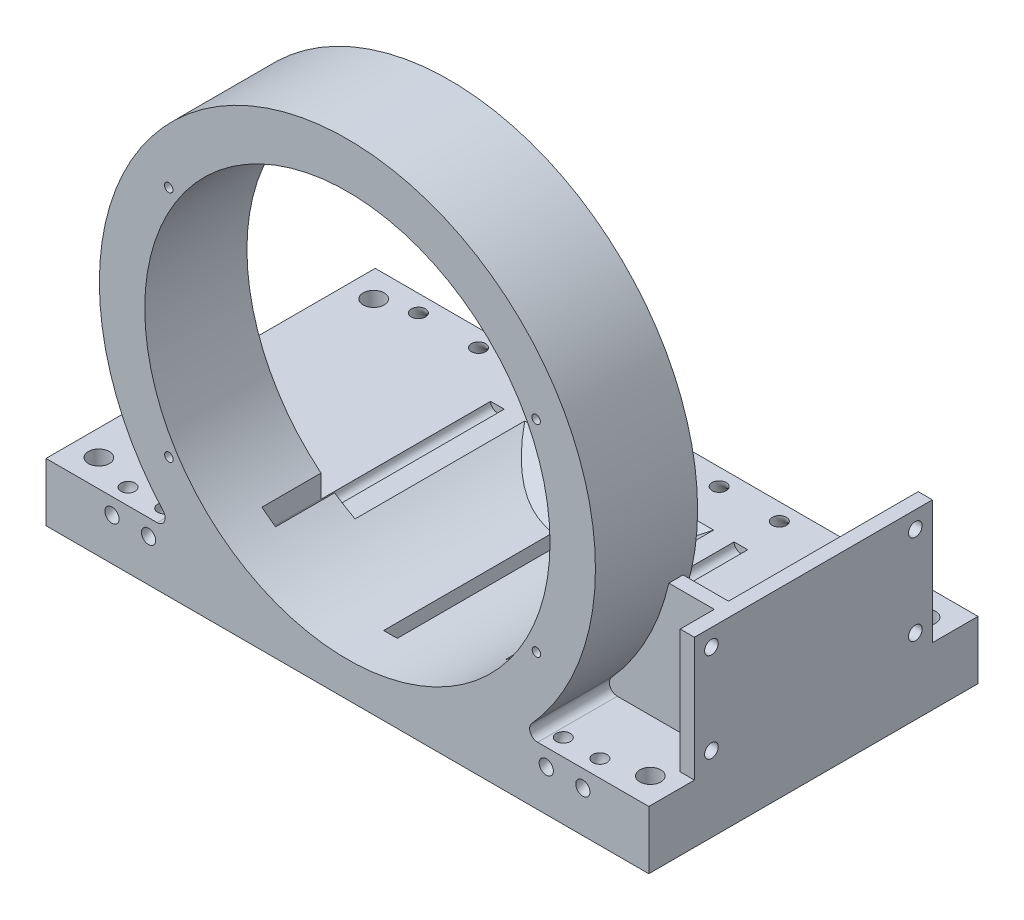
SolidWorks part; units mm, degrees
ref_plane "Front Plane" through (0, 0, 0) normal (0, 0, 1) x (1, 0, 0)
ref_plane "Top Plane" through (0, 0, 0) normal (0, 1, 0) x (1, 0, 0)
ref_plane "Right Plane" through (0, 0, 0) normal (1, 0, 0) x (0, 0, -1)
sketch "Sketch1" plane through (0, 0, 0) normal (0, 0, 1) x (1, 0, 0)
  line L0 (-34.1117, 43.7782) -> (34.1117, 43.7782)
  line L4 (28.448, -40.0843) -> (28.448, -35.2709)
  line L5 (-67.4363, -40.1112) -> (-38.3566, -40.1112)
  line L6 (-67.4363, -40.1112) -> (-67.4363, -53.1541)
  line L7 (-67.4363, -53.1541) -> (67.4363, -53.1541)
  line L8 (67.4363, -40.1112) -> (67.4363, -53.1541)
  line L9 (1.2065, -45.2975) -> (1.2065, -49.1871)
  line L10 (-1.2065, -45.2975) -> (-1.2065, -49.1871)
  line L11 (-45.339, 0) -> (45.339, 0) construction
  line L12 (-28.448, -35.2709) -> (-28.448, -40.0843)
  line L13 (38.3566, -40.1112) -> (67.4363, -40.1112)
  line L14 (26.035, -37.0877) -> (26.035, -40.0843)
  line L15 (0, 45.339) -> (0, -45.339) construction
  line L16 (-26.035, -40.0843) -> (-26.035, -37.0877)
  line L17 (-39.989, 26.0985) -> (-39.9308, -26.0985) construction
  line L18 (42.2197, 22.3102) -> (42.298, -22.7748) construction
  arc A1 (-26.035, -37.1188) -> (-1.2065, -45.3229) centre (0, 0) ccw
  arc A2 (-34.1117, 43.7782) -> (-38.3566, -40.1112) centre (0, 0) ccw
  circle A3 centre (-39.989, 26.0985) radius 0.9525
  arc A4 (38.3566, -40.1112) -> (34.1117, 43.7782) centre (0, 0) ccw
  circle A5 centre (-39.9308, -26.0985) radius 0.9525
  circle A6 centre (42.298, -22.7748) radius 0.9525
  circle A7 centre (42.2197, 22.3102) radius 0.9525
  arc A9 (-1.2065, -49.1871) -> (1.2065, -49.1871) centre (0, -49.1871) ccw
  arc A10 (-28.448, -40.0843) -> (-26.035, -40.0843) centre (-27.2415, -40.0843) ccw
  arc A11 (1.2065, -45.3229) -> (26.035, -37.1188) centre (0, 0) ccw
  arc A12 (26.035, -40.0843) -> (28.448, -40.0843) centre (27.2415, -40.0843) ccw
  arc A13 (28.448, -35.3035) -> (-28.448, -35.3035) centre (0, 0) ccw
  point P8 (0, -45.339)
  point P24 (-39.9599, 0)
  point P25 (42.2589, -0.2323)
  point P26 (0, 0)
  point P28 (0, 0)
  dimension "D1" = 90.678
  dimension "D2" = 10.16
  dimension "D4" = 1.905
  dimension "D5" = 1.905
  dimension "D6" = 1.905
  dimension "D7" = 1.905
  dimension "D10" = 82.296
  dimension "D3" = 2.413
  dimension "D8" = 52.197
  dimension "D9" = 45.085
  dimension "D11" = 82.296
  dimension "D12" = 47.752
  dimension "D13" = 47.752
extrude "Boss-Extrude1" add sketch "Sketch1" along normal blind 22.86 contours L13 A4 L0 A1 A2 L5 L6 L7 L8 region at (-22.9528, 42.1173, 0)
sketch "Sketch2" plane through (0, 0, 0) normal (0, 0, -1) x (-1, 0, 0)
  line L0 (21.1356, -40.1112) -> (26.0353, -40.1112)
  line L1 (-67.4363, -53.1541) -> (67.4363, -53.1541)
  line L2 (-67.4363, -53.1541) -> (-67.4363, -40.1112)
  line L3 (-67.4363, -40.1112) -> (-28.4477, -40.1112)
  line L4 (67.4363, -53.1541) -> (67.4363, -40.1112)
  line L5 (1.2065, -49.1871) -> (1.2065, -45.3229)
  line L6 (28.4477, -40.1112) -> (67.4363, -40.1112)
  line L7 (-1.2065, -45.3229) -> (-1.2065, -49.1871)
  line L8 (-26.0353, -40.1112) -> (-21.1356, -40.1112)
  arc A0 (-21.1356, -40.1112) -> (-1.2065, -45.3229) centre (0, 0) ccw
  arc A1 (-28.4477, -40.1112) -> (-26.0353, -40.1112) centre (-27.2415, -40.0843) ccw
  arc A2 (-1.2065, -49.1871) -> (1.2065, -49.1871) centre (0, -49.1871) ccw
  arc A3 (26.0353, -40.1112) -> (28.4477, -40.1112) centre (27.2415, -40.0843) ccw
  arc A4 (1.2065, -45.3229) -> (21.1356, -40.1112) centre (0, 0) ccw
extrude "Boss-Extrude2" add sketch "Sketch2" along normal blind 50.8 contours L2 L3 A1 L8 A0 L7 A2 L5 A4 L0 A3 L6 L4 L1
sketch "Sketch3" plane through (0, 0, 0) normal (0, 0, -1) x (-1, 0, 0)
  line L0 (-28.448, 40.2554) -> (-28.448, 35.2709)
  line L1 (-28.448, 35.2709) -> (-26.035, 37.0877)
  line L2 (-26.035, 37.0877) -> (-26.035, 40.2554)
  line L3 (28.448, 40.2554) -> (28.448, 35.3035)
  line L4 (28.448, 35.3035) -> (26.0792, 37.0877)
  line L5 (26.0792, 37.0877) -> (26.035, 40.2554)
  line L6 (-25.7175, 36.9294) -> (-25.7175, 40.2554)
  line L7 (-28.7655, 40.2554) -> (-28.7655, 34.6344)
  line L8 (-28.7655, 34.6344) -> (-25.7175, 36.9294)
  line L9 (25.7639, 36.9278) -> (25.7175, 40.251)
  line L10 (28.7655, 34.6668) -> (25.7639, 36.9278)
  line L11 (28.7655, 40.2554) -> (28.7655, 34.6668)
  arc A0 (-26.035, 40.2554) -> (-28.448, 40.2554) centre (-27.2415, 40.2554) ccw
  arc A1 (28.448, 40.2554) -> (26.0355, 40.2217) centre (27.2415, 40.2554) ccw
  arc A2 (28.448, -35.3035) -> (11.7939, 43.7782) centre (0, 0) ccw construction
  arc A3 (-25.7175, 40.2554) -> (-28.7655, 40.2554) centre (-27.2415, 40.2554) ccw
  arc A4 (28.7655, 40.2554) -> (25.7181, 40.2129) centre (27.2415, 40.2554) ccw
  arc M5 (11.7939, 43.7782) -> (28.448, -35.3035) centre (0, 0) cw
  dimension "D1" = 0.3175
extrude "Cut-Extrude1" cut sketch "Sketch3" against normal blind 13.208 contours L3 A1 L5 M5 | L2 A0 L0 L1 region at (27.3142, 38.671, 0) region at (-27.3223, 38.7004, 0)
sketch "Sketch4" plane through (0, 0, 22.86) normal (0, 0, 1) x (1, 0, 0)
  line L0 (-26.035, -40.0843) -> (-26.035, -37.1188)
  line L2 (-28.448, -35.3035) -> (-28.448, -40.0843)
  line L3 (-1.2065, -45.3229) -> (-1.2065, -49.1871)
  line L5 (1.2065, -45.2975) -> (1.2065, -49.1871)
  line L6 (28.448, -40.0843) -> (28.448, -35.3035)
  line L7 (1.1905, -45.3234) -> (1.2065, -45.2975)
  line L8 (26.035, -37.1188) -> (26.035, -40.0843)
  arc A0 (-28.448, -40.0843) -> (-26.035, -40.0843) centre (-27.2415, -40.0843) ccw
  arc A1 (-1.2065, -49.1871) -> (1.2065, -49.1871) centre (0, -49.1871) ccw
  arc A2 (26.035, -40.0843) -> (28.448, -40.0843) centre (27.2415, -40.0843) ccw
  arc A3 (-28.448, -35.3035) -> (-26.035, -37.1188) centre (0, 0) ccw
  arc A4 (-1.2065, -45.3229) -> (1.2065, -45.3229) centre (0, 0) ccw
  arc A5 (26.035, -37.1188) -> (28.448, -35.3035) centre (0, 0) ccw
  line M14 (28.448, -35.3035) -> (28.448, -40.0843)
  arc M15 (28.448, -40.0843) -> (26.035, -40.0843) centre (27.2415, -40.0843) cw
  line M16 (26.035, -40.0843) -> (26.035, -37.1188)
  line M18 (1.2065, -45.3229) -> (1.2065, -49.1871)
  arc M19 (1.2065, -49.1871) -> (-1.2065, -49.1871) centre (0, -49.1871) cw
  line M20 (-1.2065, -49.1871) -> (-1.2065, -45.3229)
  line M22 (-26.035, -37.1188) -> (-26.035, -40.0843)
  arc M23 (-26.035, -40.0843) -> (-28.448, -40.0843) centre (-27.2415, -40.0843) cw
  line M24 (-28.448, -40.0843) -> (-28.448, -35.3035)
extrude "Boss-Extrude3" add sketch "Sketch4" against normal blind 9.652 contours A3 M24 M23 M22 | A4 M20 M19 M18 | A5 M16 M15 M14 region at (-27.3175, -38.611, 22.86) region at (0, -47.7417, 22.86) region at (27.3175, -38.611, 22.86)
sketch "Sketch6" plane through (67.4363, 0, 0) normal (1, 0, 0) x (0, 0, -1)
  line L2 (20.8189, -46.8236) -> (20.8189, -53.1541)
  line L3 (50.8, -40.1112) -> (50.8, -45.3976)
  line L5 (-22.86, -53.1541) -> (50.8, -53.1541) construction
  line L6 (20.8189, -53.1541) -> (50.8, -53.1541)
  line L9 (50.8, -53.1541) -> (50.8, -45.3976)
  line L10 (50.8, -53.1541) -> (50.8, -40.1112) construction
  line L12 (50.8, -40.1112) -> (37.9477, -40.1112)
  line L13 (-22.86, -40.1112) -> (50.8, -40.1112) construction
  line L14 (37.9477, -40.1112) -> (20.8189, -46.8236)
extrude "Boss-Extrude5" add sketch "Sketch6" against normal blind 116.84 contours L14 L2 L6 L9 L3 L12
sketch "Sketch7" plane through (0, -53.1541, 0) normal (0, -1, 0) x (1, 0, 0)
  line L0 (-61.6911, -44.7061) -> (-61.6911, 16.7661) construction
  line L1 (0, -13.97) -> (-61.6911, 16.7661)
  line L2 (-61.6911, 16.7661) -> (61.6911, -44.7061)
  line L3 (0, -13.97) -> (-61.6911, -13.97) construction
  line L4 (0, 22.86) -> (0, -50.8) construction
  line L5 (-67.4363, 22.86) -> (67.4363, 22.86) construction
  line L6 (67.4363, -50.8) -> (-67.4363, -50.8) construction
  circle A0 centre (-61.6911, 16.7661) radius 2.3495
  circle A1 centre (61.6911, -44.7061) radius 2.3495
  circle A2 centre (-61.6911, -44.7061) radius 2.3495
  circle A3 centre (61.6911, 16.7661) radius 2.3495
  dimension "D3" = 4.699
  dimension "D4" = 4.699
  dimension "D1" = 68.9238
  dimension "D2" = 137.8477
  dimension "D5" = 61.4723
extrude "Cut-Extrude2" cut sketch "Sketch7" against normal blind 25.4 contours A0 | A2 | A1 | A3 region at (-63.9134, -53.1541, 17.2891) region at (-61.6911, -53.1541, -44.7061)
sketch "Sketch8" plane through (0, -40.1112, 0) normal (0, 1, 0) x (1, 0, 0)
  line L0 (-67.4363, 50.8) -> (67.4363, 50.8)
  line L1 (-67.4363, 50.8) -> (-67.4363, 46.99)
  line L2 (-67.4363, -22.86) -> (-67.4363, 50.8) construction
  line L3 (-67.4363, 46.99) -> (67.4363, 46.99) construction
  line L4 (67.4363, -22.86) -> (67.4363, 50.8) construction
  line L5 (-67.4363, -22.86) -> (-67.4363, -17.78)
  line L6 (-67.4363, -17.78) -> (67.4363, -17.78) construction
  line L7 (-0.1263, 46.99) -> (0, -17.78) construction
  circle A0 centre (-53.9743, 46.99) radius 1.5875
  circle A1 centre (-40.5123, 46.99) radius 1.5875
  circle A2 centre (-27.0503, 46.99) radius 1.5875
  circle A3 centre (-13.5883, 46.99) radius 1.5875
  circle A4 centre (-0.1263, 46.99) radius 1.5875
  circle A5 centre (13.3357, 46.99) radius 1.5875
  circle A6 centre (26.7977, 46.99) radius 1.5875
  circle A7 centre (40.2597, 46.99) radius 1.5875
  circle A8 centre (53.7217, 46.99) radius 1.5875
  circle A9 centre (53.7217, -17.78) radius 1.5875
  circle A10 centre (44.6271, -17.78) radius 1.5875
  circle A11 centre (-53.7213, -17.9895) radius 1.5875
  circle A12 centre (-44.6267, -17.9541) radius 1.5875
  dimension "D1" = 3.175
  dimension "D6" = 3.175
  dimension "D7" = 3.175
  dimension "D2" = 3.81
  dimension "D3" = 13.462
  dimension "D5" = 5.08
  dimension "D4" = 9
revolve "Cut-Revolve1" cut sketch "Sketch8" angle 360 about L0 region at (-53.9743, -40.1112, -46.99) region at (-40.5123, -40.1112, -46.99) region at (-27.0503, -40.1112, -46.99) region at (-13.5883, -40.1112, -46.99) region at (-0.1263, -40.1112, -46.99) region at (13.3357, -40.1112, -46.99) region at (26.7977, -40.1112, -46.99) region at (40.2597, -40.1112, -46.99) region at (53.7217, -40.1112, -46.99)
sketch "Sketch9" plane through (0, -40.1112, 0) normal (0, 1, 0) x (1, 0, 0)
  line L0 (-67.4363, -22.86) -> (-67.4363, -19.05)
  line L1 (-67.4363, -22.86) -> (-67.4363, 50.8) construction
  line L2 (-67.4363, -19.05) -> (67.4363, -19.05) construction
  line L3 (67.4363, -22.86) -> (67.4363, 50.8) construction
  line L4 (0, -19.05) -> (-0.1263, 45.4025)
  circle A0 centre (44.4978, -19.05) radius 1.5875
  circle A1 centre (52.6808, -19.05) radius 1.5875
  circle A2 centre (-0.1263, 46.99) radius 1.5875 construction
  circle A3 centre (-52.6804, -19.2565) radius 1.5875
  circle A4 centre (-44.4975, -19.2244) radius 1.5875
  dimension "D2" = 3.175
  dimension "D3" = 3.175
  dimension "D1" = 3.81
revolve "Cut-Revolve2" cut sketch "Sketch9" angle 360 about axis through (0, -40.1112, 22.86) along (1, 0, 0) region at (-52.6804, -40.1112, 18.4698) region at (52.6808, -40.1112, 18.3762) region at (52.6808, -40.1112, 19.7238) region at (44.4978, -40.1112, 18.3762) region at (44.4978, -40.1112, 19.7238) region at (-44.4975, -40.1112, 18.4555) region at (-44.4975, -40.1112, 19.805) region at (-52.6804, -40.1112, 19.8201)
fillet "Fillet1" radius 1.778 2 edges at (-38.3566, -40.1112, 11.43) (38.3566, -40.1112, 11.43)
sketch "Sketch11" plane through (0, 0, 0) normal (0, 0, -1) x (-1, 0, 0)
  line L1 (28.448, -35.3035) -> (28.448, -40.0843) construction
  line L2 (28.4477, -40.1112) -> (42.5584, -40.1112) construction
  line L3 (34.1117, 43.7782) -> (11.7939, 43.7782) construction
  line L5 (-26.035, 40.2554) -> (-26.035, 37.1188) construction
  line L6 (-11.7939, 43.7782) -> (-34.1117, 43.7782) construction
  line L7 (-42.5584, -40.1112) -> (-28.4477, -40.1112) construction
  line L8 (-28.448, -40.0843) -> (-28.448, -35.3035) construction
  line L9 (-28.448, 35.3035) -> (-28.448, 40.2554) construction
  line L11 (28.448, -35.3035) -> (28.448, -40.0843)
  line L12 (28.4477, -40.1112) -> (42.5584, -40.1112)
  line L13 (34.1117, 43.7782) -> (11.7939, 43.7782)
  line L15 (-26.035, 40.2554) -> (-26.035, 37.1188)
  line L16 (-11.7939, 43.7782) -> (-34.1117, 43.7782)
  line L17 (-42.5584, -40.1112) -> (-28.4477, -40.1112)
  line L18 (-28.448, -40.0843) -> (-28.448, -35.3035)
  line L19 (-28.448, 35.3035) -> (-28.448, 40.2554)
  line L20 (-28.829, 40.2554) -> (-28.829, 34.9931)
  line L21 (-25.654, 40.2554) -> (-25.654, 37.3831)
  line L22 (-11.7939, 43.7782) -> (11.7939, 43.7782)
  line L23 (0, 43.7782) -> (0, 33.6339)
  line L24 (-25.7175, -40.0843) -> (-25.7175, -36.9533)
  line L25 (-28.7655, -34.6335) -> (-28.7655, -40.0843)
  line L26 (-26.0353, -40.1112) -> (-21.1356, -40.1112)
  line L27 (-26.035, -37.1188) -> (-26.035, -40.0843)
  line L28 (-26.0353, -40.1112) -> (-21.1356, -40.1112)
  line L29 (-26.035, -37.1188) -> (-26.035, -40.0843)
  line L30 (-28.448, -35.3035) -> (-28.448, -40.0843)
  line L31 (-26.035, -40.0843) -> (-26.035, -37.1188)
  line L32 (-28.448, -35.3035) -> (-28.448, -40.0843)
  line L33 (-26.035, -40.0843) -> (-26.035, -37.1188)
  line L34 (-1.2065, -45.3229) -> (-1.2065, -49.1871)
  line L35 (1.2065, -49.1871) -> (1.2065, -45.3229)
  line L36 (-1.2065, -45.3229) -> (-1.2065, -49.1871)
  line L37 (1.2065, -49.1871) -> (1.2065, -45.3229)
  line L38 (1.524, -49.1871) -> (1.524, -44.9957)
  line L39 (-1.524, -44.9957) -> (-1.524, -49.1871)
  line L40 (1.524, -44.9957) -> (1.524, -49.1871)
  line L41 (-1.524, -49.1871) -> (-1.524, -44.9957)
  line L42 (-1.2065, -49.1871) -> (-1.2065, -45.3229)
  line L43 (1.2065, -45.3229) -> (1.2065, -49.1871)
  line L44 (26.035, -40.0843) -> (26.035, -37.1188)
  line L45 (28.448, -35.3035) -> (28.448, -40.0843)
  line L46 (26.035, -37.1188) -> (26.035, -40.0843)
  line L47 (26.0353, -40.1112) -> (21.1356, -40.1112)
  line L48 (28.7655, -34.6335) -> (28.7655, -40.0843)
  line L49 (25.7175, -40.0843) -> (25.7175, -36.9533)
  line L50 (25.654, 40.2554) -> (25.654, 37.3831)
  line L51 (28.829, 40.2554) -> (28.829, 34.9931)
  line L53 (28.448, -40.0843) -> (28.448, -35.3035)
  line L54 (42.5584, -40.1112) -> (28.4477, -40.1112)
  line L55 (11.7939, 43.7782) -> (34.1117, 43.7782)
  line L62 (28.448, 40.2554) -> (28.448, 35.3035)
  line L63 (28.448, -35.3035) -> (28.448, -40.0843)
  line L64 (28.4477, -40.1112) -> (42.5584, -40.1112)
  line L65 (34.1117, 43.7782) -> (11.7939, 43.7782)
  line L66 (26.0792, 37.0877) -> (26.035, 40.2554)
  line L68 (28.448, -35.3035) -> (28.448, -40.0843)
  line L69 (28.4477, -40.1112) -> (42.5584, -40.1112)
  line L70 (34.1117, 43.7782) -> (11.7939, 43.7782)
  arc A0 (28.448, -35.3035) -> (28.448, 35.3035) centre (0, 0) ccw construction
  arc A1 (28.4477, -40.1112) -> (28.448, -40.0843) centre (27.2415, -40.0843) ccw construction
  arc A2 (41.2373, -37.1433) -> (42.5584, -40.1112) centre (42.5584, -38.3332) ccw construction
  arc A3 (41.2373, -37.1433) -> (34.1117, 43.7782) centre (0, 0) ccw construction
  arc A4 (26.0792, 37.0877) -> (11.7939, 43.7782) centre (0, 0) ccw construction
  arc A5 (28.448, 40.2554) -> (26.035, 40.2554) centre (27.2415, 40.2554) ccw construction
  arc A6 (-26.035, 40.2554) -> (-28.448, 40.2554) centre (-27.2415, 40.2554) ccw construction
  arc A7 (-11.7939, 43.7782) -> (-26.035, 37.1188) centre (0, 0) ccw construction
  arc A8 (-34.1117, 43.7782) -> (-41.2373, -37.1433) centre (0, 0) ccw construction
  arc A9 (-42.5584, -40.1112) -> (-41.2373, -37.1433) centre (-42.5584, -38.3332) ccw construction
  arc A10 (-28.448, -40.0843) -> (-28.4477, -40.1112) centre (-27.2415, -40.0843) ccw construction
  arc A11 (-28.448, 35.3035) -> (-28.448, -35.3035) centre (0, 0) ccw construction
  arc A12 (28.448, -35.3035) -> (28.448, 35.3035) centre (0, 0) ccw
  arc A13 (28.4477, -40.1112) -> (28.448, -40.0843) centre (27.2415, -40.0843) ccw
  arc A14 (41.2373, -37.1433) -> (42.5584, -40.1112) centre (42.5584, -38.3332) ccw
  arc A15 (41.2373, -37.1433) -> (34.1117, 43.7782) centre (0, 0) ccw
  arc A16 (26.0792, 37.0877) -> (11.7939, 43.7782) centre (0, 0) ccw
  arc A18 (-26.035, 40.2554) -> (-28.448, 40.2554) centre (-27.2415, 40.2554) ccw
  arc A19 (-11.7939, 43.7782) -> (-26.035, 37.1188) centre (0, 0) ccw
  arc A20 (-34.1117, 43.7782) -> (-41.2373, -37.1433) centre (0, 0) ccw
  arc A21 (-42.5584, -40.1112) -> (-41.2373, -37.1433) centre (-42.5584, -38.3332) ccw
  arc A22 (-28.448, -40.0843) -> (-28.4477, -40.1112) centre (-27.2415, -40.0843) ccw
  arc A23 (-28.448, 35.3035) -> (-28.448, -35.3035) centre (0, 0) ccw
  circle A24 centre (-27.2415, 40.2554) radius 1.5875
  arc A25 (-28.7655, -40.0843) -> (-25.7175, -40.0843) centre (-27.2415, -40.0843) ccw
  arc A26 (-28.7655, -34.6335) -> (-25.7175, -36.9533) centre (0, 0) ccw
  arc A27 (-26.0353, -40.1112) -> (-26.035, -40.0843) centre (-27.2415, -40.0843) ccw
  arc A28 (-26.035, -37.1188) -> (-21.1356, -40.1112) centre (0, 0) ccw
  arc A29 (-26.0353, -40.1112) -> (-26.035, -40.0843) centre (-27.2415, -40.0843) ccw
  arc A30 (-26.035, -37.1188) -> (-21.1356, -40.1112) centre (0, 0) ccw
  arc A31 (-28.448, -35.3035) -> (-26.035, -37.1188) centre (0, 0) ccw
  arc A32 (-28.448, -40.0843) -> (-26.035, -40.0843) centre (-27.2415, -40.0843) ccw
  arc A33 (-28.448, -35.3035) -> (-26.035, -37.1188) centre (0, 0) ccw
  arc A34 (-28.448, -40.0843) -> (-26.035, -40.0843) centre (-27.2415, -40.0843) ccw
  arc A35 (-1.2065, -45.3229) -> (1.2065, -45.3229) centre (0, 0) ccw
  arc A36 (-1.2065, -49.1871) -> (1.2065, -49.1871) centre (0, -49.1871) ccw
  arc A37 (-1.2065, -45.3229) -> (1.2065, -45.3229) centre (0, 0) ccw
  arc A38 (-1.2065, -49.1871) -> (1.2065, -49.1871) centre (0, -49.1871) ccw
  arc A39 (-1.524, -49.1871) -> (1.524, -49.1871) centre (0, -49.1871) ccw
  arc A40 (-1.524, -44.9957) -> (1.524, -44.9957) centre (0, 0) ccw
  arc A41 (28.448, -40.0843) -> (26.035, -40.0843) centre (27.2415, -40.0843) cw
  arc A42 (28.448, -35.3035) -> (26.035, -37.1188) centre (0, 0) cw
  arc A43 (26.035, -37.1188) -> (21.1356, -40.1112) centre (0, 0) cw
  arc A44 (26.0353, -40.1112) -> (26.035, -40.0843) centre (27.2415, -40.0843) cw
  arc A45 (28.7655, -34.6335) -> (25.7175, -36.9533) centre (0, 0) cw
  arc A46 (28.7655, -40.0843) -> (25.7175, -40.0843) centre (27.2415, -40.0843) cw
  arc A48 (28.448, 35.3035) -> (28.448, -35.3035) centre (0, 0) cw
  arc A49 (28.448, -40.0843) -> (28.4477, -40.1112) centre (27.2415, -40.0843) cw
  arc A50 (42.5584, -40.1112) -> (41.2373, -37.1433) centre (42.5584, -38.3332) cw
  arc A51 (34.1117, 43.7782) -> (41.2373, -37.1433) centre (0, 0) cw
  arc A52 (11.7939, 43.7782) -> (26.035, 37.1188) centre (0, 0) cw
  arc A54 (28.829, 40.2554) -> (25.654, 40.2554) centre (27.2415, 40.2554) ccw
  circle A55 centre (0, 0) radius 45.339
  arc A60 (28.448, -35.3035) -> (28.448, 35.3035) centre (0, 0) ccw
  arc A61 (28.4477, -40.1112) -> (28.448, -40.0843) centre (27.2415, -40.0843) ccw
  arc A62 (41.2373, -37.1433) -> (42.5584, -40.1112) centre (42.5584, -38.3332) ccw
  arc A63 (41.2373, -37.1433) -> (34.1117, 43.7782) centre (0, 0) ccw
  arc A64 (26.0792, 37.0877) -> (11.7939, 43.7782) centre (0, 0) ccw
  arc A65 (28.448, 40.2554) -> (26.035, 40.2554) centre (27.2415, 40.2554) ccw
  arc A66 (28.448, -35.3035) -> (28.448, 35.3035) centre (0, 0) ccw
  arc A67 (28.4477, -40.1112) -> (28.448, -40.0843) centre (27.2415, -40.0843) ccw
  arc A68 (41.2373, -37.1433) -> (42.5584, -40.1112) centre (42.5584, -38.3332) ccw
  arc A69 (41.2373, -37.1433) -> (34.1117, 43.7782) centre (0, 0) ccw
  arc A70 (26.0792, 37.0877) -> (11.7939, 43.7782) centre (0, 0) ccw
  arc M27 (-28.448, 40.2554) -> (-26.035, 40.2554) centre (-27.2415, 40.2554) cw
  line M28 (-26.035, 40.2554) -> (-26.035, 37.1188)
  arc M29 (-26.035, 37.1188) -> (-11.7939, 43.7782) centre (0, 0) cw
  arc M34 (-28.4477, -40.1112) -> (-28.448, -40.0843) centre (-27.2415, -40.0843) cw
  line M35 (-28.448, -40.0843) -> (-28.448, -35.3035)
  arc M36 (-28.448, -35.3035) -> (-28.448, 35.3035) centre (0, 0) cw
  line M37 (-28.448, 35.3035) -> (-28.448, 40.2554)
  dimension "D1" = 3.175
  dimension "D2" = 0
  dimension "D3" = 0
  dimension "D4" = 0
  dimension "D5" = 0.3175
  dimension "D6" = 0.3175
  dimension "D7" = 0
extrude "Cut-Extrude3" cut sketch "Sketch11" against normal up to surface (13.208 mm away) contours A24 L20 M36 M37 | A24 L19 M27 M28 | A24 L15 L21 M29 | A34 L17 A25 L28 | A30 L29 A29 L28 A25 L24 | L25 A25 L17 M34 M35 M36 | A40 L39 A39 L38 A38 L36 A37 L37 | A46 L48 A12 L11 A13 L12 | A46 L12 A41 L47 | A46 L47 A41 L44 A43 L49 | A16 region at (-28.6081, -37.6424, 0) region at (-25.8783, -38.6696, 0) region at (-28.6065, -40.1452, 0) region at (-28.6866, 35.2073, 0) region at (-1.462, -47.2502, 0) region at (25.837, 38.4116, 0) region at (27.2415, -41.5744, 0) region at (25.8783, -38.6696, 0) region at (25.7909, 39.7197, 0) region at (28.6081, -37.6424, 0) region at (28.6466, 37.3546, 0) up to face at (-27.2453, -38.4544, 13.208)
sketch "Sketch12" plane through (0, 0, 0) normal (0, 0, 1) x (1, 0, 0)
  line L0 (28.7653, -40.1112) -> (28.4477, -40.1112) construction
  line L1 (26.0353, -40.1112) -> (25.7177, -40.1112) construction
  line L2 (1.2065, -45.3229) -> (1.2065, -49.1871) construction
  line L3 (-1.2065, -49.1871) -> (-1.2065, -45.3229) construction
  line L4 (-1.524, -45.3134) -> (-1.524, -49.1871) construction
  line L5 (1.524, -49.1871) -> (1.524, -45.3134) construction
  line L6 (-25.7177, -40.1112) -> (-26.0353, -40.1112) construction
  line L7 (-28.4477, -40.1112) -> (-28.7653, -40.1112) construction
  line L8 (28.7653, -40.1112) -> (28.4477, -40.1112)
  line L9 (26.0353, -40.1112) -> (25.7177, -40.1112)
  line L10 (1.2065, -45.3229) -> (1.2065, -49.1871)
  line L11 (-1.2065, -49.1871) -> (-1.2065, -45.3229)
  line L12 (-1.524, -45.3134) -> (-1.524, -49.1871)
  line L13 (1.524, -49.1871) -> (1.524, -45.3134)
  line L14 (-25.7177, -40.1112) -> (-26.0353, -40.1112)
  line L15 (-28.4477, -40.1112) -> (-28.7653, -40.1112)
  line L16 (-28.4477, -40.1112) -> (-26.0353, -40.1112)
  line L17 (-1.2065, -45.3229) -> (1.2065, -45.3229)
  line L18 (26.0353, -40.1112) -> (28.4477, -40.1112)
  line L20 (1.524, -45.3134) -> (-1.524, -45.3134)
  line L21 (1.524, -45.3134) -> (1.524, -39.544)
  line L22 (1.524, -39.544) -> (-1.524, -39.544)
  line L23 (-1.524, -45.3134) -> (-1.524, -39.544)
  arc A0 (26.0353, -40.1112) -> (28.4477, -40.1112) centre (27.2415, -40.0843) ccw construction
  arc A1 (25.7177, -40.1112) -> (28.7653, -40.1112) centre (27.2415, -40.0843) ccw construction
  arc A2 (1.2065, -45.3229) -> (1.524, -45.3134) centre (0, 0) ccw construction
  arc A3 (-1.2065, -49.1871) -> (1.2065, -49.1871) centre (0, -49.1871) ccw construction
  arc A4 (-1.524, -45.3134) -> (-1.2065, -45.3229) centre (0, 0) ccw construction
  arc A5 (-1.524, -49.1871) -> (1.524, -49.1871) centre (0, -49.1871) ccw construction
  arc A6 (-28.4477, -40.1112) -> (-26.0353, -40.1112) centre (-27.2415, -40.0843) ccw construction
  arc A7 (-28.7653, -40.1112) -> (-25.7177, -40.1112) centre (-27.2415, -40.0843) ccw construction
  arc A8 (26.0353, -40.1112) -> (28.4477, -40.1112) centre (27.2415, -40.0843) ccw
  arc A9 (25.7177, -40.1112) -> (28.7653, -40.1112) centre (27.2415, -40.0843) ccw
  arc A10 (1.2065, -45.3229) -> (1.524, -45.3134) centre (0, 0) ccw
  arc A11 (-1.2065, -49.1871) -> (1.2065, -49.1871) centre (0, -49.1871) ccw
  arc A12 (-1.524, -45.3134) -> (-1.2065, -45.3229) centre (0, 0) ccw
  arc A13 (-1.524, -49.1871) -> (1.524, -49.1871) centre (0, -49.1871) ccw
  arc A14 (-28.4477, -40.1112) -> (-26.0353, -40.1112) centre (-27.2415, -40.0843) ccw
  arc A15 (-28.7653, -40.1112) -> (-25.7177, -40.1112) centre (-27.2415, -40.0843) ccw
  arc M1 (1.524, -45.3134) -> (1.2065, -45.3229) centre (0, 0) cw
  line M2 (1.2065, -45.3229) -> (1.2065, -49.1871)
  arc M3 (1.2065, -49.1871) -> (-1.2065, -49.1871) centre (0, -49.1871) cw
  line M4 (-1.2065, -49.1871) -> (-1.2065, -45.3229)
  arc M5 (-1.2065, -45.3229) -> (-1.524, -45.3134) centre (0, 0) cw
  line M6 (-1.524, -45.3134) -> (-1.524, -49.1871)
  arc M7 (-1.524, -49.1871) -> (1.524, -49.1871) centre (0, -49.1871) ccw
  line M8 (1.524, -49.1871) -> (1.524, -45.3134)
extrude "Cut-Extrude4" cut sketch "Sketch12" against normal up to vertex (37.9477 mm away) contours L18 A8 | L9 A9 L8 A8 | M8 M1 M2 M3 M4 M5 M6 M7 | L17 M4 M3 M2 | L15 A15 L14 A14 | L16 A14 | L20 L17 M1 M5 | L23 L20 L21 L22 region at (27.2415, -41.5744, 0) region at (27.2415, -40.6109, 0) region at (1.3671, -45.3804, 0) region at (0, -47.7363, 0) region at (0, -45.318, 0) region at (0, -42.4287, 0) region at (-27.2415, -41.5744, 0) region at (-27.2415, -40.6109, 0) up to point (-21.1356, -40.1112, -37.9477)
sketch "Sketch13" plane through (0, 0, 0) normal (0, 0, -1) x (-1, 0, 0)
  line L0 (-34.1117, 43.7782) -> (34.1117, 43.7782)
  circle A0 centre (0, 0) radius 45.339
  circle A1 centre (0, 0) radius 55.499
  line M10 (-11.7939, 43.7782) -> (-34.1117, 43.7782)
extrude "Boss-Extrude6" add sketch "Sketch13" against normal up to surface (22.86 mm away) contours L0 A1 A0 M10 region at (0, 48.706, 0) up to face at (-51.0929, -43.7147, 22.86)
sketch "Sketch14" plane through (67.4363, 0, 0) normal (1, 0, 0) x (0, 0, -1)
  line L0 (13.97, -40.1112) -> (13.97, 13.5172)
  line L1 (-8.8392, -16.2352) -> (36.7792, -16.2352)
  line L2 (-8.8392, -16.2352) -> (-8.8392, -36.3012)
  line L3 (-8.8392, -36.3012) -> (36.7792, -36.3012)
  line L4 (36.7792, -16.2352) -> (36.7792, -36.3012)
  line L5 (-22.86, -40.1112) -> (50.8, -40.1112) construction
  line L14 (-12.6492, -12.4252) -> (40.5892, -12.4252)
  line L15 (40.5892, -12.4252) -> (40.5892, -40.1112)
  line L16 (-12.6492, -40.1112) -> (40.5892, -40.1112)
  line L17 (-12.6492, -12.4252) -> (-12.6492, -40.1112)
  circle A0 centre (-8.8392, -16.2352) radius 1.524
  circle A1 centre (36.7792, -36.3012) radius 1.524
  circle A2 centre (-8.8392, -36.3012) radius 1.524
  circle A3 centre (36.7792, -16.2352) radius 1.524
  line M8 (50.8, -40.1112) -> (-22.86, -40.1112)
  dimension "D1" = 3.048
  dimension "D2" = 3.048
  dimension "D3" = 3.048
  dimension "D4" = 3.048
  dimension "D5" = 20.066
  dimension "D6" = 45.6184
  dimension "D7" = 22.8092
  dimension "D8" = 3.81
extrude "Boss-Extrude8" add sketch "Sketch14" against normal blind 3.175 contours A3 L4 A1 L3 L0 L15 L14 L1 M8 | A2 L2 A0 L1 L0 L14 L17 L3 M8 | A2 L3 L0 L1 A0 L2 | A3 L1 L0 L3 A1 L4 region at (67.4363, -39.7271, -0.6604) region at (67.4363, -38.2062, -14.3541) region at (67.4363, -26.2682, -2.6518) region at (67.4363, -26.2682, -25.2882)
ref_plane "Plane3" through (0, 0, 5.0292) normal (0, 0, 1) x (1, 0, 0)
ref_plane "Plane4" through (0, 0, -32.9692) normal (0, 0, -1) x (-1, 0, 0)
sketch "Sketch16" plane through (0, 0, 5.0292) normal (0, 0, 1) x (1, 0, 0)
  line L0 (67.4363, -40.1112) -> (67.4363, -12.4252) construction
  line L1 (67.4363, -12.4252) -> (64.2613, -12.4252) construction
  line L2 (64.2613, -12.4252) -> (64.2613, -40.1112) construction
  line L3 (64.2613, -40.1112) -> (67.4363, -40.1112) construction
  line L4 (-42.5584, -40.1112) -> (-67.4363, -40.1112) construction
  line L5 (-67.4363, -40.1112) -> (-67.4363, -53.1541) construction
  line L6 (-67.4363, -53.1541) -> (67.4363, -53.1541) construction
  line L7 (67.4363, -53.1541) -> (67.4363, -40.1112) construction
  line L8 (67.4363, -40.1112) -> (42.5584, -40.1112) construction
  line L9 (67.4363, -40.1112) -> (67.4363, -12.4252)
  line L10 (67.4363, -12.4252) -> (64.2613, -12.4252)
  line L11 (64.2613, -12.4252) -> (64.2613, -40.1112)
  line L12 (64.2613, -40.1112) -> (67.4363, -40.1112)
  line L13 (-42.5584, -40.1112) -> (-67.4363, -40.1112)
  line L14 (-67.4363, -40.1112) -> (-67.4363, -53.1541)
  line L15 (-67.4363, -53.1541) -> (67.4363, -53.1541)
  line L16 (67.4363, -53.1541) -> (67.4363, -40.1112)
  line L17 (67.4363, -40.1112) -> (42.5584, -40.1112)
  line L18 (64.2613, -12.4252) -> (54.0902, -12.4252)
  arc A0 (41.2373, -37.1433) -> (42.5584, -40.1112) centre (42.5584, -38.3332) ccw construction
  arc A1 (41.2373, -37.1433) -> (-41.2373, -37.1433) centre (0, 0) ccw construction
  arc A2 (-42.5584, -40.1112) -> (-41.2373, -37.1433) centre (-42.5584, -38.3332) ccw construction
  arc A3 (41.2373, -37.1433) -> (42.5584, -40.1112) centre (42.5584, -38.3332) ccw
  arc A4 (41.2373, -37.1433) -> (-41.2373, -37.1433) centre (0, 0) ccw
  arc A5 (-42.5584, -40.1112) -> (-41.2373, -37.1433) centre (-42.5584, -38.3332) ccw
extrude "Boss-Extrude9" add sketch "Sketch16" against normal blind 3.175 contours A4 A3 L17 L11 L18 region at (55.6406, -28.3627, 5.0292)
sketch "Sketch17" plane through (0, 0, -32.9692) normal (0, 0, -1) x (-1, 0, 0)
  line L0 (67.4363, -40.1112) -> (-67.4363, -40.1112) construction
  line L1 (-67.4363, -40.1112) -> (-67.4363, -53.1541) construction
  line L2 (-67.4363, -53.1541) -> (67.4363, -53.1541) construction
  line L3 (67.4363, -53.1541) -> (67.4363, -40.1112) construction
  line L4 (-67.4363, -12.4252) -> (-67.4363, -40.1112) construction
  line L5 (-67.4363, -40.1112) -> (-64.2613, -40.1112) construction
  line L6 (-64.2613, -40.1112) -> (-64.2613, -12.4252) construction
  line L7 (-64.2613, -12.4252) -> (-67.4363, -12.4252) construction
  line L8 (67.4363, -40.1112) -> (-67.4363, -40.1112)
  line L9 (-67.4363, -40.1112) -> (-67.4363, -53.1541)
  line L10 (-67.4363, -53.1541) -> (67.4363, -53.1541)
  line L11 (67.4363, -53.1541) -> (67.4363, -40.1112)
  line L12 (-67.4363, -12.4252) -> (-67.4363, -40.1112)
  line L13 (-67.4363, -40.1112) -> (-64.2613, -40.1112)
  line L14 (-64.2613, -40.1112) -> (-64.2613, -12.4252)
  line L15 (-64.2613, -12.4252) -> (-67.4363, -12.4252)
  line L16 (-64.2613, -12.4252) -> (-43.8863, -40.1112)
extrude "Boss-Extrude10" add sketch "Sketch17" against normal blind 3.175 contours L16 L14 L8 region at (57.4696, -30.8825, -32.9692)
sketch "Sketch18" plane through (0, 0, 0) normal (0, 0, -1) x (-1, 0, 0)
  line L0 (-45.339, -0.0411) -> (45.339, -0.0411)
  line L1 (-1.524, 45.2312) -> (-1.524, 49.1049)
  line L2 (1.524, -49.1871) -> (1.524, -45.3134)
  line L3 (-1.524, -45.3134) -> (-1.524, -49.1871)
  line L4 (1.524, -49.1871) -> (1.524, -45.3134)
  line L5 (-1.524, -45.3134) -> (-1.524, -49.1871)
  line L6 (1.524, 49.1049) -> (1.524, 45.2312)
  line L9 (-1.524, 45.2312) -> (-1.524, 41.2188)
  line L10 (-1.524, 41.2188) -> (1.524, 41.2188)
  line L11 (1.524, 45.2312) -> (1.524, 41.2188)
  arc A0 (-28.829, 34.9931) -> (-28.7655, -35.0453) centre (0, 0) ccw construction
  arc A1 (28.7655, -35.0453) -> (28.829, 34.9931) centre (0, 0) ccw construction
  arc A2 (-1.524, -45.3134) -> (1.524, -45.3134) centre (0, 0) ccw
  arc A3 (-1.524, -49.1871) -> (1.524, -49.1871) centre (0, -49.1871) ccw
  arc A4 (-1.524, -45.3134) -> (1.524, -45.3134) centre (0, 0) ccw
  arc A5 (-1.524, -49.1871) -> (1.524, -49.1871) centre (0, -49.1871) ccw
  arc A6 (-1.524, 49.1049) -> (1.524, 49.1049) centre (0, 49.1049) cw
  arc M15 (-25.654, 37.3831) -> (25.654, 37.3831) centre (0, 0) cw
  dimension "D1" = 0
extrude "Cut-Extrude5" cut sketch "Sketch18" against normal up to surface (13.208 mm away) contours L11 L6 L1 L9 L10 M15 | A6 L1 L6 M15 region at (0, 43.2747, 0) region at (0, 47.8278, 0) up to face at (0, -47.6376, 13.208)
